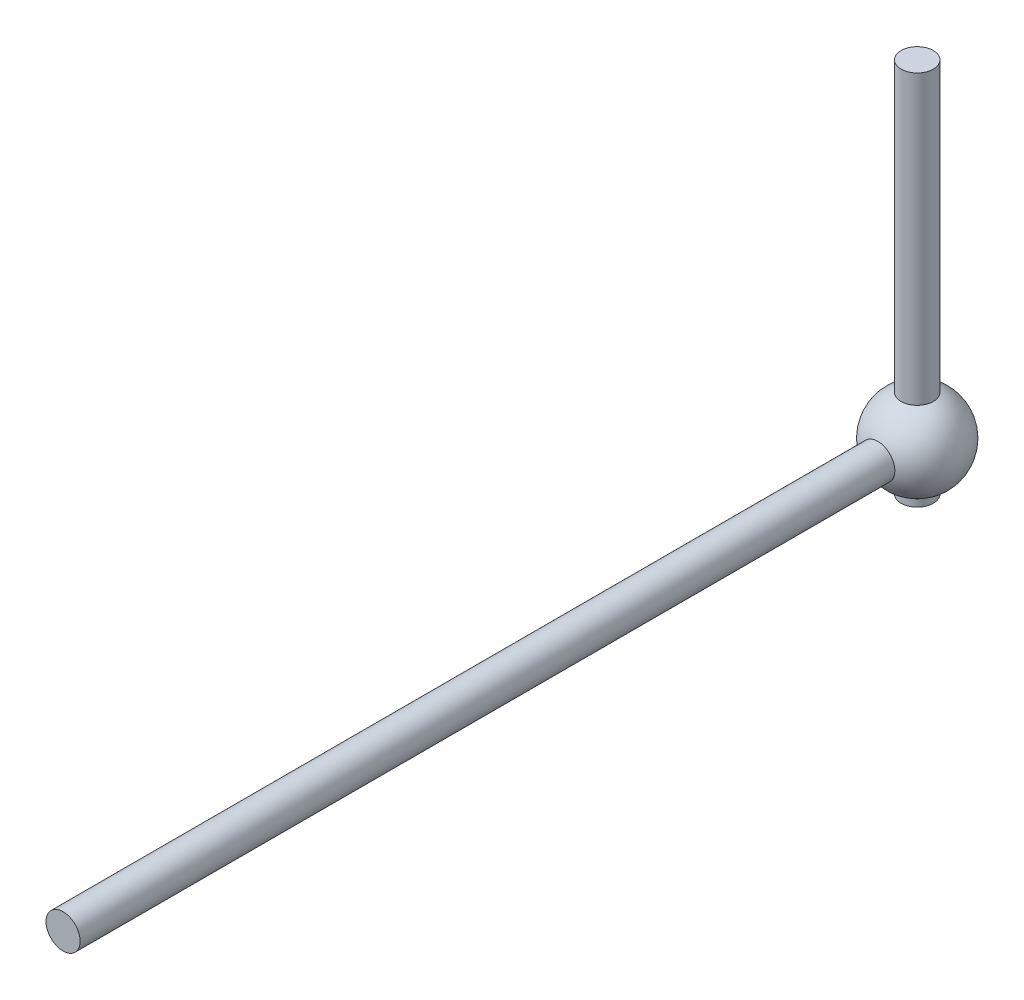
SolidWorks part; units mm, degrees
material "Plain Carbon Steel"
ref_plane "Front Plane" through (0, 0, 0) normal (0, 0, 1) x (1, 0, 0)
ref_plane "Top Plane" through (0, 0, 0) normal (0, 1, 0) x (1, 0, 0)
ref_plane "Right Plane" through (0, 0, 0) normal (1, 0, 0) x (0, 0, -1)
sketch "Sketch1" plane through (0, 0, 0) normal (0, 0, 1) x (1, 0, 0)
  circle A0 centre (0, 0) radius 3.175
  dimension "D1" = 6.35
extrude "Boss-Extrude1" add sketch "Sketch1" along normal blind 159
sketch "Sketch2" plane through (0, 0, 0) normal (0, 0, 1) x (1, 0, 0)
  line L0 (0, -9) -> (0, 61) construction
  line L1 (0, -9) -> (3, -9)
  line L2 (3, -9) -> (3, -7.4162)
  line L3 (3, 7.4162) -> (3, 61)
  line L4 (3, 61) -> (0, 61)
  line L5 (0, 61) -> (0, -9)
  arc A0 (3, -7.4162) -> (3, 7.4162) centre (0, 0) ccw
revolve "Revolve1" add sketch "Sketch2" angle 360 about L0
